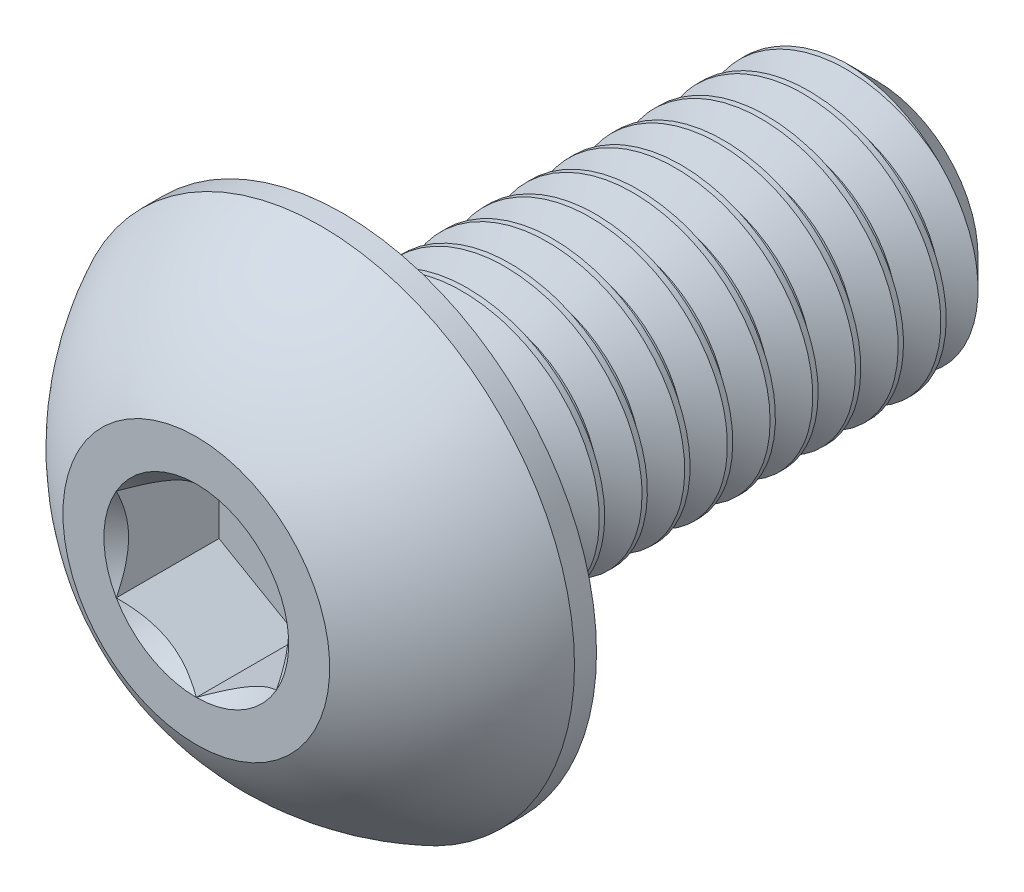
SolidWorks part; units mm, degrees
note: '?' marks a value the reader was unsure of.
ref_plane "Front" through (0, 0, 0) normal (0, 0, 1) x (1, 0, 0)
ref_plane "Top" through (0, 0, 0) normal (0, 1, 0) x (1, 0, 0)
ref_plane "Right" through (0, 0, 0) normal (1, 0, 0) x (0, 0, -1)
sketch "Sketch1" plane through (0, 0, 0) normal (1, 0, 0) x (0, 0, -1)
  line L2 (2.75, 2.5) -> (12.75, 2.5)
  line L3 (12.75, 2.5) -> (12.75, 0)
  line L4 (12.75, 0) -> (2.75, 0)
  line L6 (2.3375, 4.75) -> (2.75, 4.75) construction
  line L7 (12.75, 2.5) -> (12.75, -2.5) construction
  line L8 (0, 0) -> (2.75, 0) construction
  line L9 (2.75, 4.75) -> (2.75, -4.75) construction
  line L11 (2.75, 2.5) -> (2.75, 0)
  line L13 (0, 1.5) -> (0, -1.5) construction
  line L14 (0, 1.5) -> (0, 2.5) construction
  arc A3 (0, 2.5) -> (2.3375, 4.75) centre (4.6581, 0) cw construction
  dimension "D1" = 0.4125
revolve "Revolve1" add sketch "Sketch1" angle 360 mid plane about L4
sketch "Sketch3" plane through (0, 0, -12.75) normal (0, 0, -1) x (-1, 0, 0)
  circle A0 centre (0, 0) radius 2.5
curve "Helix/Spiral1" pitch 0.8 height 10.8 turns 13.5
chamfer "Chamfer1" distance 0.6 angle 45 1 edges at (0, 2.5, -12.75)
sketch "Sketch7" plane through (0, 0, 0) normal (1, 0, 0) x (0, 0, -1)
  line L6 (2.3375, 4.75) -> (2.75, 4.75) construction
  line L8 (0, 0) -> (2.75, 0) construction
  line L11 (2.75, 4.75) -> (2.75, -4.75) construction
  line L12 (2.3375, 4.75) -> (2.75, 4.75)
  line L13 (0, 0) -> (2.75, 0)
  line L14 (0, 1.5) -> (0, -1.5) construction
  line L15 (2.75, 4.75) -> (2.75, 0)
  line L16 (0, 2.5) -> (0, 0)
  arc A2 (2.3375, 4.75) -> (0, 2.5) centre (4.6581, 0) ccw construction
  arc A3 (2.3375, 4.75) -> (0, 2.5) centre (4.6581, 0) ccw
revolve "Revolve2" add sketch "Sketch7" angle 360 mid plane about L13
sketch "Sketch5" plane through (0, 0, 0) normal (0, 0, 1) x (1, 0, 0)
  line L1 (1.5, -0.866) -> (1.5, 0.866)
  line L2 (1.5, 0.866) -> (0, 1.7321)
  line L3 (0, 1.7321) -> (-1.5, 0.866)
  line L4 (-1.5, 0.866) -> (-1.5, -0.866)
  line L5 (-1.5, -0.866) -> (0, -1.7321)
  line L6 (0, -1.7321) -> (1.5, -0.866)
  circle A0 centre (0, 0) radius 1.5 construction
extrude "Cut-Extrude2" cut sketch "Sketch5" against normal blind 1.925
sketch "Sketch6" plane through (0, 0, 0) normal (0, 0, 1) x (1, 0, 0)
  circle A0 centre (0, 0) radius 1.7321
extrude "Cut-Extrude3" cut sketch "Sketch6" against normal blind 1.925 draft 45
sketch "Sketch2" plane through (0, 0, 0) normal (1, 0, 0) x (0, 0, -1)
  line L0 (12.15, 2.5) -> (12.85, 2.5)
  line L1 (12.85, 2.5) -> (12.55, 1.9804)
  line L2 (12.55, 1.9804) -> (12.45, 1.9804)
  line L3 (12.45, 1.9804) -> (12.15, 2.5)
  line L4 (12.3, 2.2402) -> (12.7, 2.2402) construction
  dimension "D1" = 60
  dimension "D2" = 0.1
  dimension "D3" = 0.4
sweep "Cut-Sweep1" cut profiles "Sketch2" path "Helix/Spiral1"
sketch "Sketch10" plane through (0, 0, 0) normal (1, 0, 0) x (0, 0, -1)
  line L0 (12.75, 2.5) -> (12.75, -2.5) construction
  point P0 (11.55, -2.5)
  dimension "D1" = 1.2
ref_axis "Center Axis 1" through (0, 0, -8.1113) along (0, 0, 1)?
ref_plane "Contact Plane 1" through (0, 0, -2.75) normal (0, 0, -1) x (-1, 0, 0)
ref_plane "Contact Plane 2" through (0, 0, 0) normal (0, 0, 1) x (1, 0, 0)
move or copy body "Body-Move/Copy1" [suppressed] bodies to move or copy 114
equation "\"D3@Helix/Spiral1\" = \"Lg@Sketch1\" + \"D4@Helix/Spiral1\""
equation "\"D2@Sketch2\" = \"D4@Helix/Spiral1\" * .125"
equation "\"D3@Sketch2\" = \"D4@Helix/Spiral1\" * .5"
equation "\"D1@Chamfer1\" = \"D4@Helix/Spiral1\" * .75"
equation "\"D1@Cut-Extrude2\" = \"Head Ht@Sketch1\" * .7"
equation "\"D1@Sketch1\" = \"Head Ht@Sketch1\" * .15"
equation "\"D1@Sketch10\" = \"D4@Helix/Spiral1\" * 1.5"
equation "\"D1@Cut-Extrude3\" = \"D1@Cut-Extrude2\""
